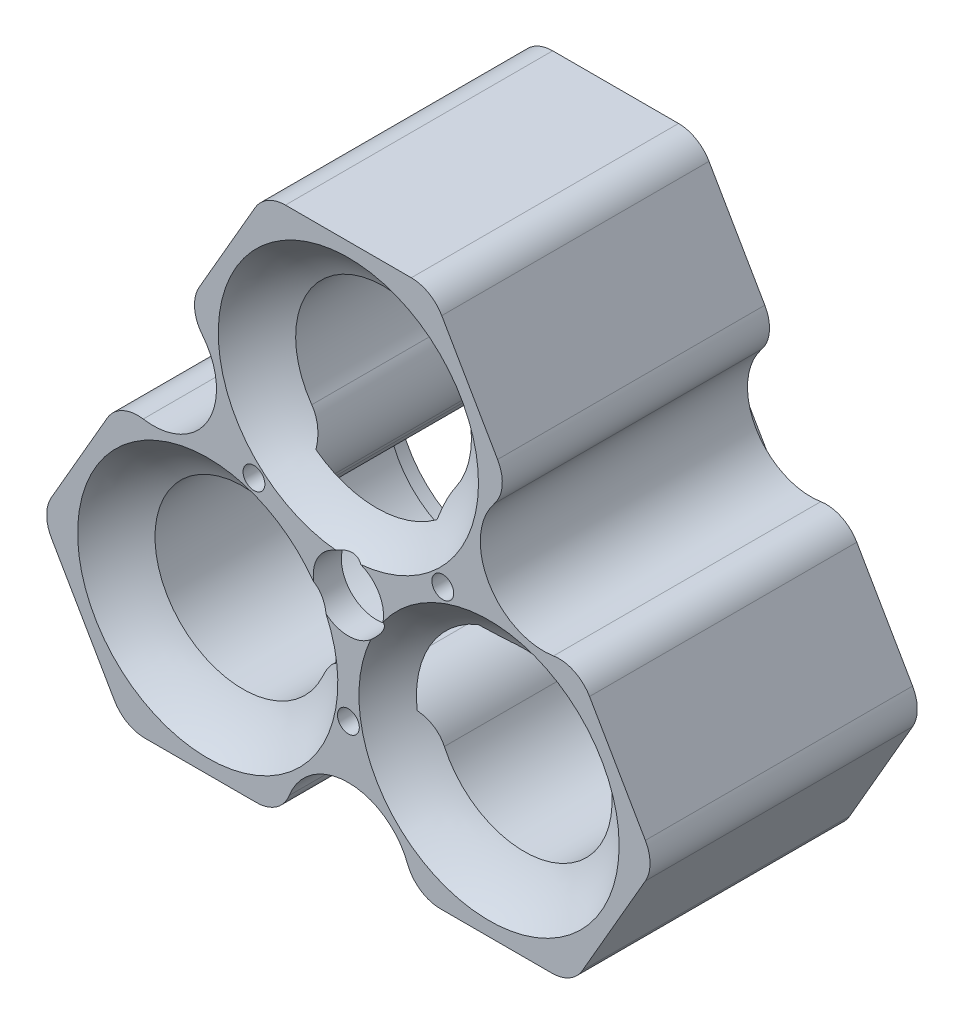
SolidWorks part; units mm, degrees
ref_plane "前视基准面" through (0, 0, 0) normal (0, 0, 1) x (1, 0, 0)
ref_plane "上视基准面" through (0, 0, 0) normal (0, 1, 0) x (1, 0, 0)
ref_plane "右视基准面" through (0, 0, 0) normal (1, 0, 0) x (0, 0, -1)
sketch "草图1" plane through (0, 0, 0) normal (0, 0, 1) x (1, 0, 0)
  line L1 (-9.7628, 6.1843) -> (-10.2372, 5.3627)
  line L2 (-0.4744, -11.547) -> (0.4744, -11.547)
  line L3 (10.2372, 5.3627) -> (9.7628, 6.1843)
  circle A0 centre (0, 0) radius 11.547 construction
  arc A1 (10.2076, 15.8791) -> (-10.2076, 15.8791) centre (0, 23.094) ccw
  circle A2 centre (0, 23.094) radius 6
  arc A3 (8.6479, -16.7796) -> (18.8555, 0.9005) centre (20, -11.547) ccw
  circle A4 centre (20, -11.547) radius 6
  arc A5 (-18.8555, 0.9005) -> (-8.6479, -16.7796) centre (-20, -11.547) ccw
  circle A6 centre (-20, -11.547) radius 6
  arc A7 (-0.4744, -11.547) -> (-8.6479, -16.7796) centre (-0.4744, -20.547) ccw
  arc A8 (0.4744, -11.547) -> (8.6479, -16.7796) centre (0.4744, -20.547) cw
  arc A9 (10.2372, 5.3627) -> (18.8555, 0.9005) centre (18.0314, 9.8627) ccw
  arc A10 (9.7628, 6.1843) -> (10.2076, 15.8791) centre (17.557, 10.6843) cw
  arc A11 (-9.7628, 6.1843) -> (-10.2076, 15.8791) centre (-17.557, 10.6843) ccw
  arc A12 (-10.2372, 5.3627) -> (-18.8555, 0.9005) centre (-18.0314, 9.8627) cw
  circle A13 centre (0, 0) radius 5
  dimension "D2" = 25
  dimension "D3" = 12
  dimension "D1" = 9
  dimension "D5" = 10
  dimension "D4" = 3
sketch "草图8" plane through (0, 0, 0) normal (0, 0, 1) x (1, 0, 0)
  line L0 (0, -87.188) -> (0, 0) construction
  line L1 (0, 64.094) -> (-55.507, -32.047)
  line L2 (-55.507, -32.047) -> (55.507, -32.047)
  line L3 (55.507, -32.047) -> (0, 64.094)
  line L4 (0, -87.188) -> (75.507, 43.594)
  line L5 (75.507, 43.594) -> (-75.507, 43.594)
  line L6 (-75.507, 43.594) -> (0, -87.188)
  line L7 (0, 64.094) -> (0, 0) construction
  line L8 (0, 0) -> (0, -32.047) construction
  circle A0 centre (0, 0) radius 32.047 construction
  circle A1 centre (0, 0) radius 43.594 construction
  circle A8 centre (0, 23.094) radius 12.5 construction
  circle A21 centre (-20, -11.547) radius 12.5 construction
  circle A22 centre (-27.7535, 16.0235) radius 9
  circle A23 centre (27.7535, 16.0235) radius 9
  circle A24 centre (0, -32.047) radius 9
  dimension "D2" = 8
  dimension "D3" = 18
  dimension "D4" = 3
  dimension "D1" = 8
extrude "凸台-拉伸3" add sketch "草图8" along normal blind 38 contours A24 L2 L4 L3 A23 L5 L1 A22 L6 region at (0, 0, 0)
extrude "切除-拉伸2" cut sketch "草图1" along normal blind 34 contours A2 | A6 | A4 | L1 A12 A5 A7 L2 A8 A3 A9 L3 A10 A1 A11 A2 A4 A6 | A13 region at (-7.6853, 11.1372, 0) region at (0, 23.094, 0) region at (20, -11.547, 0) region at (-20, -11.547, 0)
sketch "草图10" plane through (0, 0, 0) normal (1, 0, 0) x (0, 0, -1)
  line L0 (0, 35.594) -> (-38, 35.594) construction
  line L1 (-38, 23.8177) -> (-38, 43.594) construction
  line L2 (-38, 35.594) -> (-38, 23.094) construction
  line L3 (-38, 41.594) -> (-38, 23.094)
  line L4 (-38, 23.094) -> (-33, 23.094)
  line L5 (-33, 23.094) -> (-33, 35.594)
  line L6 (0, 0) -> (-38, 0) construction
  line L7 (-38, -11.547) -> (-38, 8.2293) construction
  arc A0 (-33, 35.594) -> (-38, 41.594) centre (-46.626, 29.3224) ccw
  dimension "D5" = 15
  dimension "D1" = 12.5
  dimension "D2" = 5
  dimension "D3" = 18.5
  dimension "D4" = 12.5
revolve "切除-旋转2" cut sketch "草图10" angle 360 about L4
pattern_circular "阵列(圆周)2" count 3 over 360 about axis through (0, 0, 0) along (0, 0, 1) of "切除-旋转2" reverse direction yes
extrude "切除-拉伸4" cut sketch "草图1<8>" along normal blind 38 contours A13 region at (0, 0, 0)
sketch "草图1<8>" plane through (0, 0, 0) normal (0, 0, 1) x (1, 0, 0) same geometry as "草图1"
fillet "圆角2" radius 5 12 edges at (-43.6714, -11.547, 19) (-31.8357, -32.047, 19) (-9, -32.047, 19) (9, -32.047, 19) (31.8357, -32.047, 19) (43.6714, -11.547, 19) (32.2535, 8.2293, 19) (23.2535, 23.8177, 19) (11.8357, 43.594, 19) (-11.8357, 43.594, 19) (-23.2535, 23.8177, 19) (-32.2535, 8.2293, 19)
sketch "草图12" plane through (0, 0, 0) normal (0, 0, -1) x (-1, 0, 0)
  line L0 (0, 0) -> (-10, 5.7735) construction
  line L1 (-10.2372, 5.3627) -> (-9.7628, 6.1843) construction
  line L2 (-10, 5.7735) -> (-19.9593, 11.5235) construction
  arc A0 (-29.1731, 7.1362) -> (-20.7666, 21.6966) centre (-27.7535, 16.0235) ccw construction
  circle A4 centre (-13.4234, 7.75) radius 1.55
  circle A5 centre (13.4234, 7.75) radius 1.55
  circle A6 centre (0, -15.5) radius 1.55
  dimension "D1" = 3.1
  dimension "D3" = 3
  dimension "D2" = 15.5
extrude "切除-拉伸5" cut sketch "草图12" against normal blind 38
sketch "草图13" plane through (0, 0, 0) normal (0, 0, -1) x (-1, 0, 0)
  line L0 (18.3162, 5.3694) -> (13.8081, 13.1776)
  line L1 (-13.8081, 13.1776) -> (-18.3162, 5.3694)
  line L2 (-4.5081, -18.547) -> (4.5081, -18.547)
  arc A0 (13.636, 16.8442) -> (-13.636, 16.8442) centre (0, 23.094) ccw
  arc A1 (7.7695, -20.2312) -> (21.4055, 3.387) centre (20, -11.547) ccw
  arc A2 (-21.4055, 3.387) -> (-7.7695, -20.2312) centre (-20, -11.547) ccw
  arc A3 (-4.5081, -18.547) -> (-7.7695, -20.2312) centre (-4.5081, -22.547) ccw
  arc A4 (4.5081, -18.547) -> (7.7695, -20.2312) centre (4.5081, -22.547) cw
  arc A5 (21.4055, 3.387) -> (18.3162, 5.3694) centre (21.7803, 7.3694) cw
  arc A6 (13.8081, 13.1776) -> (13.636, 16.8442) centre (17.2722, 15.1776) cw
  arc A7 (-18.3162, 5.3694) -> (-21.4055, 3.387) centre (-21.7803, 7.3694) cw
  arc A8 (-13.8081, 13.1776) -> (-13.636, 16.8442) centre (-17.2722, 15.1776) ccw
  dimension "D1" = 30
  dimension "D4" = 4
  dimension "D3" = 3
  dimension "D2" = 3
sketch "草图17" plane through (0, 0, 0) normal (1, 0, 0) x (0, 0, -1)
  line L1 (-3, 37.344) -> (3, 37.344)
  line L2 (-3, 37.344) -> (-3, 38.844)
  line L3 (-3, 38.844) -> (3, 38.844)
  line L4 (3, 37.344) -> (3, 38.844)
  line L5 (-3, 37.344) -> (3, 38.844) construction
  line L6 (-3, 38.844) -> (3, 37.344) construction
  point P0 (0, 38.094)
  dimension "D1" = 6
  dimension "D2" = 1.5
sweep "扫描1" add profiles "草图17" path "草图13"
